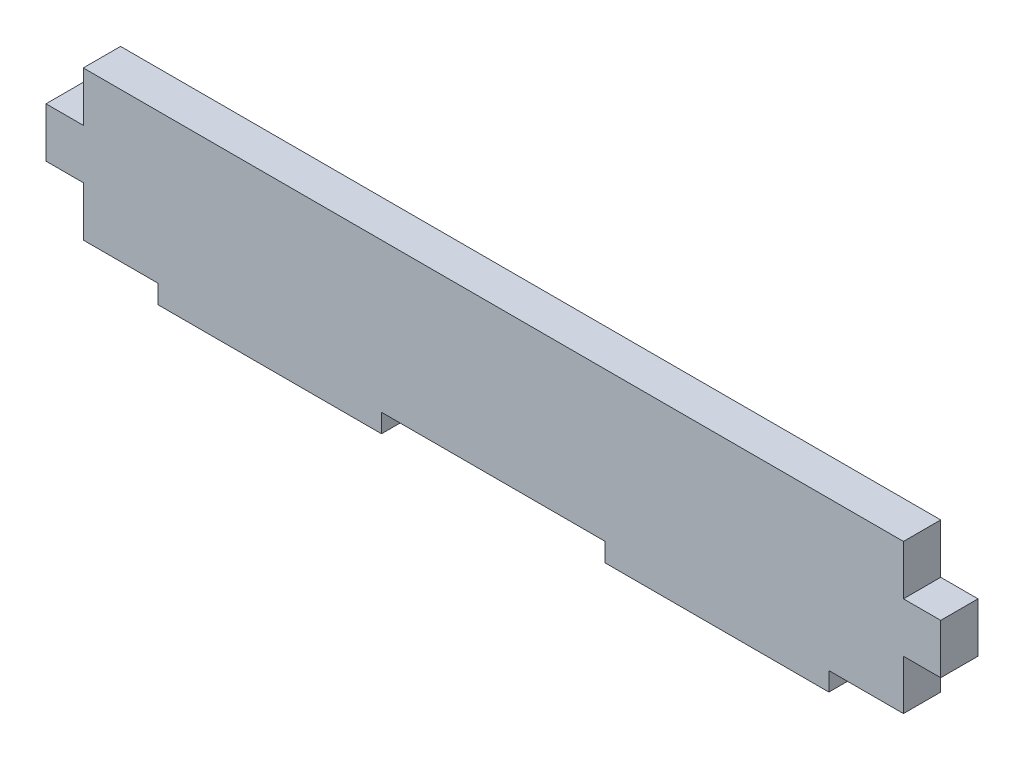
SolidWorks part; units mm, degrees
ref_plane "Front Plane" through (0, 0, 0) normal (0, 0, 1) x (1, 0, 0)
ref_plane "Top Plane" through (0, 0, 0) normal (0, 1, 0) x (1, 0, 0)
ref_plane "Right Plane" through (0, 0, 0) normal (1, 0, 0) x (0, 0, -1)
sketch "Sketch1" plane through (0, 0, 0) normal (0, 0, 1) x (1, 0, 0)
  line L1 (-152.4, -25.4) -> (152.4, -25.4)
  line L2 (-152.4, -25.4) -> (-152.4, 25.4)
  line L3 (-152.4, 25.4) -> (152.4, 25.4)
  line L4 (152.4, -25.4) -> (152.4, 25.4)
  line L5 (-152.4, -25.4) -> (152.4, 25.4) construction
  line L6 (-152.4, 25.4) -> (152.4, -25.4) construction
  point P0 (0, 0)
  dimension "D1" = 304.8
  dimension "D2" = 50.8
extrude "Boss-Extrude1" add sketch "Sketch1" along normal blind 12.7 contours L1 L3 region at (0, 0, 0)
sketch "Sketch2" plane through (0, 0, 12.7) normal (0, 0, 1) x (1, 0, 0)
  line L0 (-152.4, -25.4) -> (152.4, -25.4) construction
  line L1 (-38.1, -25.4) -> (-114.3, -25.4)
  line L2 (-38.1, -25.4) -> (-38.1, -31.75)
  line L3 (-38.1, -31.75) -> (-114.3, -31.75)
  line L4 (-114.3, -25.4) -> (-114.3, -31.75)
  line L5 (0, -6.985) -> (0, 6.985) construction
  line L6 (38.1, -31.75) -> (114.3, -31.75)
  line L7 (114.3, -25.4) -> (114.3, -31.75)
  line L8 (38.1, -25.4) -> (114.3, -25.4)
  line L9 (38.1, -25.4) -> (38.1, -31.75)
  point P12 (-38.1, -28.575)
  dimension "D1" = 76.2
  dimension "D2" = 6.35
  dimension "D3" = 76.2
extrude "Boss-Extrude2" add sketch "Sketch2" against normal blind 12.7
sketch "Sketch3" plane through (0, 0, 12.7) normal (0, 0, 1) x (1, 0, 0)
  line L0 (6.985, 0) -> (-6.985, 0) construction
  line L1 (-152.4, -25.4) -> (-139.7, -25.4)
  line L2 (-152.4, -25.4) -> (-152.4, -8.4667)
  line L3 (-152.4, -8.4667) -> (-139.7, -8.4667)
  line L4 (-139.7, -25.4) -> (-139.7, -8.4667)
  line L6 (-152.4, 8.4667) -> (-139.7, 8.4667)
  line L7 (-139.7, 25.4) -> (-139.7, 8.4667)
  line L8 (-152.4, 25.4) -> (-139.7, 25.4)
  line L9 (-152.4, 25.4) -> (-152.4, 8.4667)
  line L10 (0, -6.985) -> (0, 6.985) construction
  line L11 (152.4, 25.4) -> (152.4, 8.4667)
  line L12 (152.4, 25.4) -> (139.7, 25.4)
  line L13 (139.7, 25.4) -> (139.7, 8.4667)
  line L14 (152.4, 8.4667) -> (139.7, 8.4667)
  line L15 (152.4, -8.4667) -> (139.7, -8.4667)
  line L16 (139.7, -25.4) -> (139.7, -8.4667)
  line L17 (152.4, -25.4) -> (139.7, -25.4)
  line L18 (152.4, -25.4) -> (152.4, -8.4667)
  dimension "D1" = 16.9333
  dimension "D2" = 12.7
extrude "Cut-Extrude1" cut sketch "Sketch3" against normal through all
